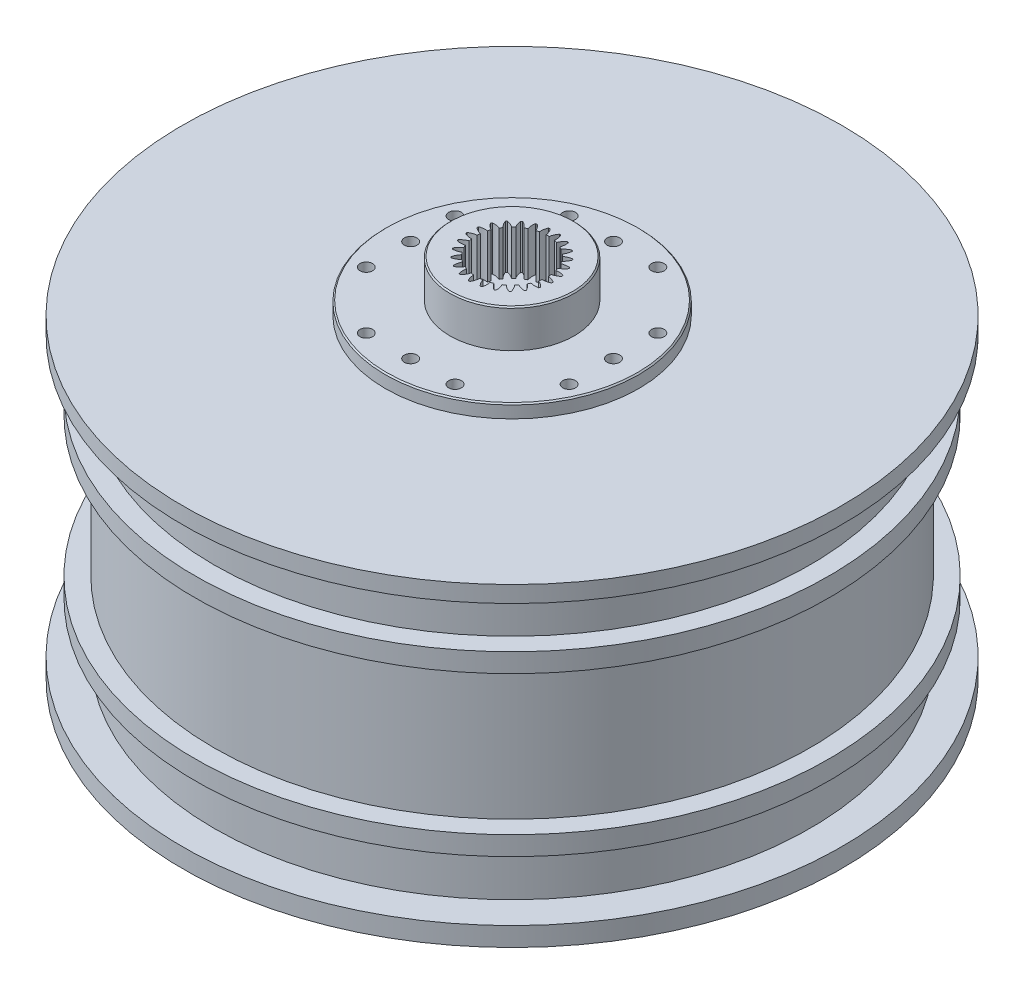
SolidWorks part; units mm, degrees
material "ABS"
ref_plane "正面" through (0, 0, 0) normal (0, 0, 1) x (1, 0, 0)
ref_plane "平面" through (0, 0, 0) normal (0, 1, 0) x (1, 0, 0)
ref_plane "右側面" through (0, 0, 0) normal (1, 0, 0) x (0, 0, -1)
sketch "ｽｹｯﾁ1" plane through (0, 0, 0) normal (0, 1, 0) x (1, 0, 0)
  circle A0 centre (0, 0) radius 10
extrude "ﾎﾞｽ - 押し出し1" add sketch "ｽｹｯﾁ1" along normal blind 2
sketch "ｽｹｯﾁ2" plane through (0, 2, 0) normal (0, 1, 0) x (1, 0, 0)
  circle A0 centre (0, 0) radius 4.9
extrude "ﾎﾞｽ - 押し出し2" add sketch "ｽｹｯﾁ2" along normal blind 3
sketch "ｽｹｯﾁ3" plane through (0, 0, 0) normal (0, -1, 0) x (1, 0, 0)
  line L0 (0, 8) -> (-3.5, 8) construction
  line L1 (0, 0) -> (0, 8) construction
  line L2 (0, 8) -> (3.5, 8) construction
  circle A0 centre (-3.5, 8) radius 0.5
  circle A1 centre (0, 8) radius 0.5
  circle A2 centre (3.5, 8) radius 0.5
  circle A3 centre (8, 0) radius 0.5
  circle A4 centre (8, 3.5) radius 0.5
  circle A5 centre (8, -3.5) radius 0.5
  circle A6 centre (0, -8) radius 0.5
  circle A7 centre (3.5, -8) radius 0.5
  circle A8 centre (-3.5, -8) radius 0.5
  circle A9 centre (-8, 0) radius 0.5
  circle A10 centre (-8, -3.5) radius 0.5
  circle A11 centre (-8, 3.5) radius 0.5
  point P29 (0, 0)
  dimension "D1" = 4
extrude "ｶｯﾄ - 押し出し1" cut sketch "ｽｹｯﾁ3" against normal blind 3
sketch "ｽｹｯﾁ4" plane through (0, 0, 0) normal (0, -1, 0) x (1, 0, 0)
  circle A0 centre (0, 0) radius 4.35
  circle A1 centre (0, 0) radius 2.9
  circle A2 centre (0, 0) radius 1.4
extrude "ｶｯﾄ - 押し出し2" cut sketch "ｽｹｯﾁ4" against normal through all contours A2 region at (0, 0, 0)
extrude "ｶｯﾄ - 押し出し3" cut sketch "ｽｹｯﾁ4<3>" against normal blind 0.45 contours A0 A1 region at (-4.227, 0, 0)
sketch "ｽｹｯﾁ4<3>" plane through (0, 0, 0) normal (0, -1, 0) x (1, 0, 0) same geometry as "ｽｹｯﾁ4"
extrude "ｶｯﾄ - 押し出し4" cut sketch "ｽｹｯﾁ4<4>" against normal blind 0.95 contours A1 A2 region at (-2.818, 0, 0)
sketch "ｽｹｯﾁ4<4>" plane through (0, 0, 0) normal (0, -1, 0) x (1, 0, 0) same geometry as "ｽｹｯﾁ4"
sketch "ｽｹｯﾁ6" plane through (0, 5, 0) normal (0, 1, 0) x (1, 0, 0)
  line L3 (-0.2102, 3.1179) -> (-0.391, 3.0951) construction
  arc A0 (0.1175, 2.809) -> (-0.1175, 2.809) centre (0, 0) ccw
  arc A1 (0.3689, 3.3803) -> (-0.3689, 3.3803) centre (0, 0) ccw
  circle A2 centre (0, 0) radius 3.125 construction
  circle A3 centre (0, 0) radius 2.9365 construction
  arc A4 (-0.1175, 2.809) -> (-0.3689, 3.3803) centre (-1.3511, 2.6072) ccw
  arc A5 (0.3689, 3.3803) -> (0.1175, 2.809) centre (1.3511, 2.6072) ccw
  arc A6 (1.1979, 3.1824) -> (0.8124, 2.6916) centre (1.9571, 2.1893) ccw
  arc A7 (0.8124, 2.6916) -> (0.5847, 2.75) centre (0, 0) ccw
  arc A8 (0.5847, 2.75) -> (0.4834, 3.3659) centre (-0.6603, 2.8613) ccw
  arc A9 (1.1979, 3.1824) -> (0.4834, 3.3659) centre (0, 0) ccw
  arc A10 (1.9517, 2.7845) -> (1.4563, 2.405) centre (2.4401, 1.6338) ccw
  arc A11 (1.4563, 2.405) -> (1.2503, 2.5182) centre (0, 0) ccw
  arc A12 (1.2503, 2.5182) -> (1.3052, 3.1399) centre (0.072, 2.9357) ccw
  arc A13 (1.9517, 2.7845) -> (1.3052, 3.1399) centre (0, 0) ccw
  arc A14 (2.5829, 2.2116) -> (2.0086, 1.9672) centre (2.7697, 0.9757) ccw
  arc A15 (2.0086, 1.9672) -> (1.8372, 2.1282) centre (0, 0) ccw
  arc A16 (1.8372, 2.1282) -> (2.0451, 2.7167) centre (0.7998, 2.8255) ccw
  arc A17 (2.5829, 2.2116) -> (2.0451, 2.7167) centre (0, 0) ccw
  arc A18 (3.0518, 1.4998) -> (2.4347, 1.4059) centre (2.9253, 0.2562) ccw
  arc A19 (2.4347, 1.4059) -> (2.3088, 1.6044) centre (0, 0) ccw
  arc A20 (2.3088, 1.6044) -> (2.6565, 2.1227) centre (1.4774, 2.5378) ccw
  arc A21 (3.0518, 1.4998) -> (2.6565, 2.1227) centre (0, 0) ccw
  arc A22 (3.3289, 0.6938) -> (2.7079, 0.7563) centre (2.8972, -0.4793) ccw
  arc A23 (2.7079, 0.7563) -> (2.6352, 0.9798) centre (0, 0) ccw
  arc A24 (2.6352, 0.9798) -> (3.1009, 1.3954) centre (2.0621, 2.0907) ccw
  arc A25 (3.3289, 0.6938) -> (3.1009, 1.3954) centre (0, 0) ccw
  arc A26 (3.3968, -0.1559) -> (2.8109, 0.0591) centre (2.6869, -1.1848) ccw
  arc A27 (2.8109, 0.0591) -> (2.7961, 0.2937) centre (0, 0) ccw
  arc A28 (2.7961, 0.2937) -> (3.3505, 0.5804) centre (2.5173, 1.5122) ccw
  arc A29 (3.3968, -0.1559) -> (3.3505, 0.5804) centre (0, 0) ccw
  arc A30 (3.2513, -0.9958) -> (2.7373, -0.6418) centre (2.3079, -1.8158) ccw
  arc A31 (2.7373, -0.6418) -> (2.7813, -0.4109) centre (0, 0) ccw
  arc A32 (2.7813, -0.4109) -> (3.3896, -0.2711) centre (2.8142, 0.8387) ccw
  arc A33 (3.2513, -0.9958) -> (3.3896, -0.2711) centre (0, 0) ccw
  arc A34 (2.9016, -1.7731) -> (2.4917, -1.3024) centre (1.7838, -2.3327) ccw
  arc A35 (2.4917, -1.3024) -> (2.5917, -1.0897) centre (0, 0) ccw
  arc A36 (2.5917, -1.0897) -> (3.2157, -1.1055) centre (2.9344, 0.1124) ccw
  arc A37 (2.9016, -1.7731) -> (3.2157, -1.1055) centre (0, 0) ccw
  arc A38 (2.3695, -2.4389) -> (2.0895, -1.8811) centre (1.1477, -2.703) ccw
  arc A39 (2.0895, -1.8811) -> (2.2393, -1.7) centre (0, 0) ccw
  arc A40 (2.2393, -1.7) -> (2.8397, -1.8705) centre (2.8702, -0.6208) ccw
  arc A41 (2.3695, -2.4389) -> (2.8397, -1.8705) centre (0, 0) ccw
  arc A42 (1.6885, -2.9516) -> (1.556, -2.3416) centre (0.4394, -2.9035) ccw
  arc A43 (1.556, -2.3416) -> (1.7462, -2.2035) centre (0, 0) ccw
  arc A44 (1.7462, -2.2035) -> (2.2853, -2.5179) centre (2.6256, -1.3151) ccw
  arc A45 (1.6885, -2.9516) -> (2.2853, -2.5179) centre (0, 0) ccw
  arc A46 (0.9014, -3.2787) -> (0.9248, -2.655) centre (-0.2965, -2.9215) ccw
  arc A47 (0.9248, -2.655) -> (1.1434, -2.5685) centre (0, 0) ccw
  arc A48 (1.1434, -2.5685) -> (1.5874, -3.0072) centre (2.216, -1.9268) ccw
  arc A49 (0.9014, -3.2787) -> (1.5874, -3.0072) centre (0, 0) ccw
  arc A50 (0.0577, -3.3999) -> (0.2355, -2.8016) centre (-1.0137, -2.756) ccw
  arc A51 (0.2355, -2.8016) -> (0.4687, -2.7722) centre (0, 0) ccw
  arc A52 (0.4687, -2.7722) -> (0.7896, -3.3074) centre (1.6673, -2.4173) ccw
  arc A53 (0.0577, -3.3999) -> (0.7896, -3.3074) centre (0, 0) ccw
  arc A54 (-0.7896, -3.3074) -> (-0.4687, -2.7722) centre (-1.6673, -2.4173) ccw
  arc A55 (-0.4687, -2.7722) -> (-0.2355, -2.8016) centre (0, 0) ccw
  arc A56 (-0.2355, -2.8016) -> (-0.0577, -3.3999) centre (1.0137, -2.756) ccw
  arc A57 (-0.7896, -3.3074) -> (-0.0577, -3.3999) centre (0, 0) ccw
  arc A58 (-1.5874, -3.0072) -> (-1.1434, -2.5685) centre (-2.216, -1.9268) ccw
  arc A59 (-1.1434, -2.5685) -> (-0.9248, -2.655) centre (0, 0) ccw
  arc A60 (-0.9248, -2.655) -> (-0.9014, -3.2787) centre (0.2965, -2.9215) ccw
  arc A61 (-1.5874, -3.0072) -> (-0.9014, -3.2787) centre (0, 0) ccw
  arc A62 (-2.2853, -2.5179) -> (-1.7462, -2.2035) centre (-2.6256, -1.3151) ccw
  arc A63 (-1.7462, -2.2035) -> (-1.556, -2.3416) centre (0, 0) ccw
  arc A64 (-1.556, -2.3416) -> (-1.6885, -2.9516) centre (-0.4394, -2.9035) ccw
  arc A65 (-2.2853, -2.5179) -> (-1.6885, -2.9516) centre (0, 0) ccw
  arc A66 (-2.8397, -1.8705) -> (-2.2393, -1.7) centre (-2.8702, -0.6208) ccw
  arc A67 (-2.2393, -1.7) -> (-2.0895, -1.8811) centre (0, 0) ccw
  arc A68 (-2.0895, -1.8811) -> (-2.3695, -2.4389) centre (-1.1477, -2.703) ccw
  arc A69 (-2.8397, -1.8705) -> (-2.3695, -2.4389) centre (0, 0) ccw
  arc A70 (-3.2157, -1.1055) -> (-2.5917, -1.0897) centre (-2.9344, 0.1124) ccw
  arc A71 (-2.5917, -1.0897) -> (-2.4917, -1.3024) centre (0, 0) ccw
  arc A72 (-2.4917, -1.3024) -> (-2.9016, -1.7731) centre (-1.7838, -2.3327) ccw
  arc A73 (-3.2157, -1.1055) -> (-2.9016, -1.7731) centre (0, 0) ccw
  arc A74 (-3.3896, -0.2711) -> (-2.7813, -0.4109) centre (-2.8142, 0.8387) ccw
  arc A75 (-2.7813, -0.4109) -> (-2.7373, -0.6418) centre (0, 0) ccw
  arc A76 (-2.7373, -0.6418) -> (-3.2513, -0.9958) centre (-2.3079, -1.8158) ccw
  arc A77 (-3.3896, -0.2711) -> (-3.2513, -0.9958) centre (0, 0) ccw
  arc A78 (-3.3505, 0.5804) -> (-2.7961, 0.2937) centre (-2.5173, 1.5122) ccw
  arc A79 (-2.7961, 0.2937) -> (-2.8109, 0.0591) centre (0, 0) ccw
  arc A80 (-2.8109, 0.0591) -> (-3.3968, -0.1559) centre (-2.6869, -1.1848) ccw
  arc A81 (-3.3505, 0.5804) -> (-3.3968, -0.1559) centre (0, 0) ccw
  arc A82 (-3.1009, 1.3954) -> (-2.6352, 0.9798) centre (-2.0621, 2.0907) ccw
  arc A83 (-2.6352, 0.9798) -> (-2.7079, 0.7563) centre (0, 0) ccw
  arc A84 (-2.7079, 0.7563) -> (-3.3289, 0.6938) centre (-2.8972, -0.4793) ccw
  arc A85 (-3.1009, 1.3954) -> (-3.3289, 0.6938) centre (0, 0) ccw
  arc A86 (-2.6565, 2.1227) -> (-2.3088, 1.6044) centre (-1.4774, 2.5378) ccw
  arc A87 (-2.3088, 1.6044) -> (-2.4347, 1.4059) centre (0, 0) ccw
  arc A88 (-2.4347, 1.4059) -> (-3.0518, 1.4998) centre (-2.9253, 0.2562) ccw
  arc A89 (-2.6565, 2.1227) -> (-3.0518, 1.4998) centre (0, 0) ccw
  arc A90 (-2.0451, 2.7167) -> (-1.8372, 2.1282) centre (-0.7998, 2.8255) ccw
  arc A91 (-1.8372, 2.1282) -> (-2.0086, 1.9672) centre (0, 0) ccw
  arc A92 (-2.0086, 1.9672) -> (-2.5829, 2.2116) centre (-2.7697, 0.9757) ccw
  arc A93 (-2.0451, 2.7167) -> (-2.5829, 2.2116) centre (0, 0) ccw
  arc A94 (-1.3052, 3.1399) -> (-1.2503, 2.5182) centre (-0.072, 2.9357) ccw
  arc A95 (-1.2503, 2.5182) -> (-1.4563, 2.405) centre (0, 0) ccw
  arc A96 (-1.4563, 2.405) -> (-1.9517, 2.7845) centre (-2.4401, 1.6338) ccw
  arc A97 (-1.3052, 3.1399) -> (-1.9517, 2.7845) centre (0, 0) ccw
  arc A98 (-0.4834, 3.3659) -> (-0.5847, 2.75) centre (0.6603, 2.8613) ccw
  arc A99 (-0.5847, 2.75) -> (-0.8124, 2.6916) centre (0, 0) ccw
  arc A100 (-0.8124, 2.6916) -> (-1.1979, 3.1824) centre (-1.9571, 2.1893) ccw
  arc A101 (-0.4834, 3.3659) -> (-1.1979, 3.1824) centre (0, 0) ccw
  circle A102 centre (0, 0) radius 2.8115
  circle A103 centre (0, 0) radius 3.4004
  point P158 (0, 0)
  dimension "D1" = 25
extrude "ｶｯﾄ - 押し出し5" cut sketch "ｽｹｯﾁ6" against normal blind 3.5 contours A51 A102 A47 A43 A39 A35 A31 A27 A23 A19 A15 A11 A7 A0 A99 A95 A91 A87 A83 A79 A75 A71 A67 A63 A59 A55 | A80 A103 A74 A102 | A84 A103 A78 A102 | A88 A103 A82 A102 | A92 A103 A86 A102 | A96 A103 A90 A102 | A100 A103 A94 A102 | A4 A103 A98 A102 | A8 A103 A5 A102 | A12 A103 A6 A102 | A16 A103 A10 A102 | A20 A103 A14 A102 | A24 A103 A18 A102 | A28 A103 A22 A102 | A32 A103 A26 A102 | A36 A103 A30 A102 | A40 A103 A34 A102 | A44 A103 A38 A102 | A48 A103 A42 A102 | A52 A103 A46 A102 | A56 A103 A50 A102 | A60 A103 A54 A102 | A64 A103 A58 A102 | A68 A103 A62 A102 | A72 A103 A66 A102 | A76 A103 A70 A102 region at (0, 5, 0) region at (0.3828, 5, -3.0303) region at (-0.3828, 5, -3.0303) region at (1.1244, 5, -2.8399) region at (-1.1244, 5, -2.8399) region at (1.7953, 5, -2.471) region at (-1.7953, 5, -2.471) region at (2.3534, 5, -1.9469) region at (-2.3534, 5, -1.9469) region at (2.7637, 5, -1.3005) region at (-2.7637, 5, -1.3005) region at (3.0003, 5, -0.5723) region at (-3.0003, 5, -0.5723) region at (3.0483, 5, 0.1918) region at (-3.0483, 5, 0.1918) region at (-2.9049, 5, 0.9439) region at (2.9049, 5, 0.9439) region at (-2.5789, 5, 1.6366) region at (2.5789, 5, 1.6366) region at (-2.0909, 5, 2.2265) region at (2.0909, 5, 2.2265) region at (-1.4715, 5, 2.6766) region at (1.4715, 5, 2.6766) region at (-0.7596, 5, 2.9584) region at (0.7596, 5, 2.9584) region at (0, 5, 3.0544)
chamfer "面取り1" distance 0.1 angle 45 3 edges at (0, 0, 10) (0, 2, 10) (0, 5, 4.9)
sketch "ｽｹｯﾁ11" plane through (0, 0, 0) normal (0, 0, 1) x (1, 0, 0)
  line L0 (18.5, -23.85) -> (23.5, -23.85)
  line L1 (2.9, 0.95) -> (23.5, 0.95)
  line L4 (23.5, -0.35) -> (23.5, -4.35)
  line L8 (2.9, 0.95) -> (2.9, -4.05)
  line L9 (23.5, -18.35) -> (23.5, -22.35)
  line L10 (2.9, 0.95) -> (26, 0.95)
  line L11 (2.9, 0.95) -> (2.9, -0.35)
  line L12 (23.5, -0.35) -> (26, -0.35)
  line L13 (26, 0.95) -> (26, -0.35)
  line L14 (23.5, -4.35) -> (25, -4.35)
  line L16 (23.5, -5.85) -> (25, -5.85)
  line L17 (25, -4.35) -> (25, -5.85)
  line L18 (23.5, -16.85) -> (25, -16.85)
  line L21 (25, -16.85) -> (25, -18.35)
  line L22 (18.5, -23.85) -> (26, -23.85)
  line L24 (23.5, -22.35) -> (26, -22.35)
  line L25 (26, -23.85) -> (26, -22.35)
  line L28 (2.9, -4.05) -> (18.5, -4.05)
  line L29 (18.5, -23.85) -> (18.5, -4.05)
  line L30 (23.5, -18.35) -> (25, -18.35)
  line L31 (23.5, -5.85) -> (23.5, -16.85)
  line L32 (23.5, -23.85) -> (26, -23.85)
  dimension "D2" = 24.8
  dimension "D4" = 1.3
  dimension "D5" = 23.1
  dimension "D6" = 1.5
  dimension "D7" = 4
  dimension "D8" = 22.1
  dimension "D9" = 1.5
  dimension "D10" = 11
  dimension "D11" = 22.1
  dimension "D12" = 23.1
  dimension "D14" = 5
  dimension "D15" = 5
sketch "ｽｹｯﾁ13" plane through (0, 0, 0) normal (0, 0, 1) x (1, 0, 0)
  line L0 (0, 0) -> (0, 6.7532)
revolve "回転1" add sketch "ｽｹｯﾁ11" angle 360 about L0 region at (18.8389, -13.95, 0)
sketch "ｽｹｯﾁ14" plane through (0, 0, 0) normal (0, 0, 1) x (1, 0, 0)
  line L0 (-20.0887, -3.1222) -> (-20.0887, -16.8787)
  line L1 (-20.0887, -16.8787) -> (-10.3358, -3.1222)
  line L2 (-10.3358, -3.1222) -> (-20.0887, -3.1222)
  point P3 (-21.4691, -17.9981)
  point P4 (-11.3082, -4.4214)
  point P5 (0, 0)
  point P6 (-19.9369, -3.1222)
  point P7 (-20.0887, -16.8787)
extrude "ﾎﾞｽ - 押し出し4" add sketch "ｽｹｯﾁ14" along normal blind 2 and the other way blind 2
pattern_circular "円形ﾊﾟﾀｰﾝ1" count 5 every 72 about axis through (0, 0, 0) along (0, 1, 0) of "ﾎﾞｽ - 押し出し4"
